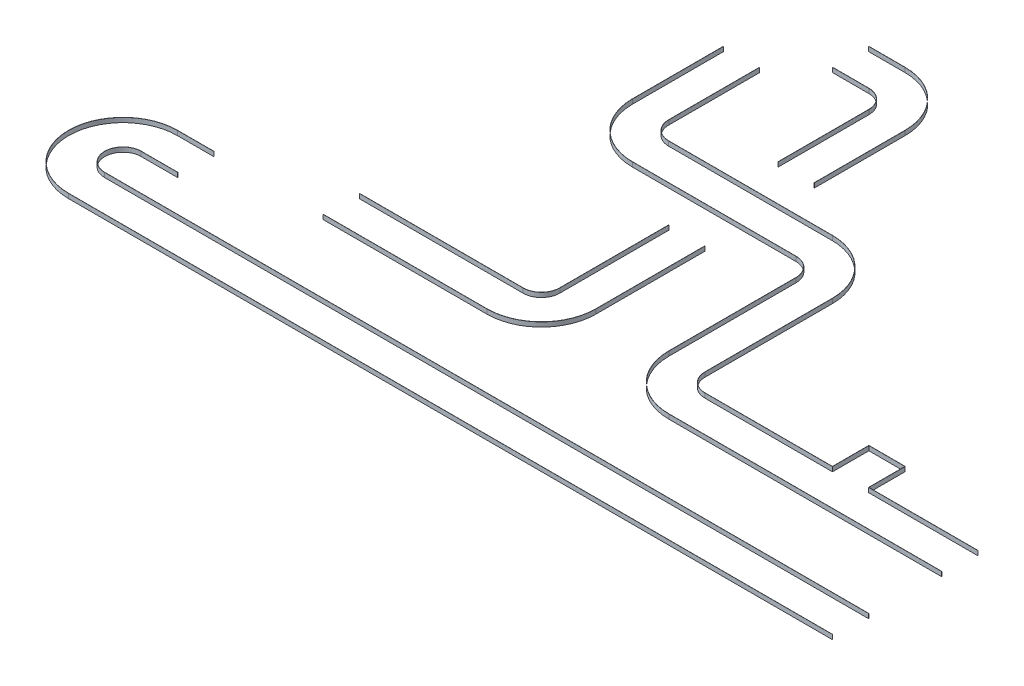
SolidWorks part; units mm, degrees
ref_plane "Front Plane" through (0, 0, 0) normal (0, 0, 1) x (1, 0, 0)
ref_plane "Top Plane" through (0, 0, 0) normal (0, 1, 0) x (1, 0, 0)
ref_plane "Right Plane" through (0, 0, 0) normal (1, 0, 0) x (0, 0, -1)
sketch "Sketch1" plane through (0, 0, 0) normal (0, 1, 0) x (1, 0, 0)
  line L0 (0, 0) -> (-12801.6, 0)
  line L1 (0, 0) -> (0, 609.6)
  line L2 (0, 609.6) -> (-12801.6, 609.6)
  line L3 (-12801.6, 1828.8) -> (-12192, 1828.8)
  line L4 (0, 1828.8) -> (0, 2438.4)
  line L5 (-12192, 1828.8) -> (-12192, 2438.4)
  line L6 (-12192, 2438.4) -> (-7620, 2438.4)
  line L7 (-12801.6, 1219.2) -> (-12192, 1219.2)
  line L8 (-12192, 1219.2) -> (-10363.2, 1219.2)
  line L9 (0, 1828.8) -> (-4572, 1828.8)
  line L10 (-10363.2, 1828.8) -> (-10363.2, 1219.2)
  line L11 (-10363.2, 1828.8) -> (-7620, 1828.8)
  line L12 (0, 2438.4) -> (-1828.8, 2438.4)
  line L13 (-5486.4, 2743.2) -> (-5486.4, 4876.8)
  line L14 (-4876.8, 2743.2) -> (-4876.8, 4876.8)
  line L15 (-5791.2, 5791.2) -> (-8534.4, 5791.2)
  line L16 (-5791.2, 5181.6) -> (-8534.4, 5181.6)
  line L17 (-8839.2, 6096) -> (-8839.2, 7620)
  line L18 (-9448.8, 6096) -> (-9448.8, 7620)
  line L19 (-9448.8, 7620) -> (-9448.8, 8839.2)
  line L20 (-9448.8, 8839.2) -> (-8229.6, 8839.2)
  line L21 (-8839.2, 7620) -> (-8229.6, 7620)
  line L22 (-8229.6, 7620) -> (-8229.6, 8229.6)
  line L23 (-8229.6, 8839.2) -> (-7620, 8839.2)
  line L24 (-8229.6, 8229.6) -> (-7620, 8229.6)
  line L25 (-7315.2, 7924.8) -> (-7315.2, 6400.8)
  line L26 (-6705.6, 7924.8) -> (-6705.6, 6400.8)
  line L27 (-7315.2, 6400.8) -> (-6705.6, 6400.8)
  line L28 (-7315.2, 4572) -> (-7315.2, 2743.2)
  line L29 (-7315.2, 4572) -> (-6705.6, 4572)
  line L30 (-6705.6, 4572) -> (-6705.6, 2743.2)
  line L31 (-2438.4, 2438.4) -> (-4572, 2438.4)
  line L33 (-2438.4, 2438.4) -> (-2438.4, 3048)
  line L34 (-2438.4, 3048) -> (-1828.8, 3048)
  line L35 (-1828.8, 2438.4) -> (-1828.8, 3048)
  arc A0 (-12801.6, 0) -> (-12801.6, 1828.8) centre (-12801.6, 914.4) cw
  arc A1 (-12801.6, 609.6) -> (-12801.6, 1219.2) centre (-12801.6, 914.4) cw
  arc A2 (-4572, 1828.8) -> (-5486.4, 2743.2) centre (-4572, 2743.2) cw
  arc A3 (-4572, 2438.4) -> (-4876.8, 2743.2) centre (-4572, 2743.2) cw
  arc A4 (-4876.8, 4876.8) -> (-5791.2, 5791.2) centre (-5791.2, 4876.8) ccw
  arc A5 (-5486.4, 4876.8) -> (-5791.2, 5181.6) centre (-5791.2, 4876.8) ccw
  arc A6 (-8534.4, 5181.6) -> (-9448.8, 6096) centre (-8534.4, 6096) cw
  arc A7 (-8534.4, 5791.2) -> (-8839.2, 6096) centre (-8534.4, 6096) cw
  arc A8 (-7620, 8839.2) -> (-6705.6, 7924.8) centre (-7620, 7924.8) cw
  arc A9 (-7620, 8229.6) -> (-7315.2, 7924.8) centre (-7620, 7924.8) cw
  arc A10 (-7620, 2438.4) -> (-7315.2, 2743.2) centre (-7620, 2743.2) ccw
  arc A11 (-7620, 1828.8) -> (-6705.6, 2743.2) centre (-7620, 2743.2) ccw
  dimension "D8" = 914.4
  dimension "D9" = 609.6
  dimension "D10" = 304.8
  dimension "D16" = 914.4
  dimension "D17" = 304.8
  dimension "D20" = 914.4
  dimension "D21" = 304.8
  dimension "D25" = 914.4
  dimension "D26" = 304.8
  dimension "D35" = 914.4
  dimension "D36" = 304.8
  dimension "D42" = 914.4
  dimension "D1" = 609.6
  dimension "D2" = 12801.6
  dimension "D3" = 12801.6
  dimension "D4" = 609.6
  dimension "D5" = 12801.6
  dimension "D6" = 609.6
  dimension "D7" = 1219.2
  dimension "D11" = 609.6
  dimension "D12" = 12192
  dimension "D13" = 1828.8
  dimension "D14" = 4572
  dimension "D15" = 3048
  dimension "D18" = 2133.6
  dimension "D19" = 2133.6
  dimension "D22" = 2743.2
  dimension "D23" = 609.6
  dimension "D24" = 609.6
  dimension "D27" = 1524
  dimension "D28" = 1524
  dimension "D29" = 1219.2
  dimension "D30" = 1219.2
  dimension "D31" = 609.6
  dimension "D32" = 609.6
  dimension "D33" = 609.6
  dimension "D34" = 609.6
  dimension "D37" = 609.6
  dimension "D38" = 1524
  dimension "D39" = 609.6
  dimension "D40" = 1828.8
  dimension "D41" = 1828.8
  dimension "D43" = 609.6
  dimension "D44" = 609.6
  dimension "D45" = 609.6
  dimension "D46" = 1828.8
extrude "Boss-Extrude1" add sketch "Sketch1" along normal blind 76.2
sketch "Sketch3" plane through (0, 76.2, 0) normal (0, 1, 0) x (1, 0, 0)
  line L1 (-12192, 2438.4) -> (-10363.2, 2438.4)
  line L2 (-12192, 2438.4) -> (-12192, 1219.2)
  line L3 (-12192, 1219.2) -> (-10363.2, 1219.2)
  line L4 (-10363.2, 2438.4) -> (-10363.2, 1219.2)
  line L5 (-9448.8, 8839.2) -> (-8229.6, 8839.2)
  line L6 (-9448.8, 8839.2) -> (-9448.8, 7620)
  line L7 (-9448.8, 7620) -> (-8229.6, 7620)
  line L8 (-8229.6, 8839.2) -> (-8229.6, 7620)
extrude "Cut-Extrude1" cut sketch "Sketch3" against normal blind 76.2
shell "Shell1" thickness 2.54 removed face at (-9601.2, 0, -914.4) removed face at (-9601.2, 76.2, -914.4)
shell "Shell2" thickness 2.54 removed face at (-7969.4369, 0, -2864.0369) removed face at (-7969.4369, 76.2, -2864.0369)
shell "Shell3" thickness 2.54 removed face at (-5194.2252, 0, -4193.6148) removed face at (-5194.2252, 76.2, -4193.6148)
shell "Shell4" thickness 2.54 removed face at (-7436.0369, 0, -7880.1631) removed face at (-7436.0369, 76.2, -7880.1631)
sketch "Sketch4" plane through (0, 76.2, 0) normal (0, 1, 0) x (1, 0, 0)
  line L0 (0, 0) -> (0, 609.6) construction
  line L1 (-2.54, 607.06) -> (0, 607.06)
  line L2 (-2.54, 607.06) -> (-2.54, 2.54)
  line L3 (-2.54, 2.54) -> (0, 2.54)
  line L4 (0, 607.06) -> (0, 2.54)
  line L5 (0, 1828.8) -> (0, 2438.4) construction
  line L6 (-2.54, 2435.86) -> (0, 2435.86)
  line L7 (-2.54, 2435.86) -> (-2.54, 1831.34)
  line L8 (-2.54, 1831.34) -> (0, 1831.34)
  line L9 (0, 2435.86) -> (0, 1831.34)
  line L11 (-12192, 1828.8) -> (-12192, 1219.2) construction
  line L12 (-12194.54, 1826.26) -> (-12192, 1826.26)
  line L13 (-12194.54, 1826.26) -> (-12194.54, 1221.74)
  line L14 (-12194.54, 1221.74) -> (-12192, 1221.74)
  line L15 (-12192, 1826.26) -> (-12192, 1221.74)
  line L16 (-10363.2, 1828.8) -> (-10363.2, 2438.4) construction
  line L17 (-10360.66, 2435.86) -> (-10363.2, 2435.86)
  line L18 (-10360.66, 2435.86) -> (-10360.66, 1831.34)
  line L19 (-10360.66, 1831.34) -> (-10363.2, 1831.34)
  line L20 (-10363.2, 2435.86) -> (-10363.2, 1831.34)
  line L21 (-6705.6, 4572) -> (-7315.2, 4572) construction
  line L22 (-7312.66, 4569.46) -> (-6708.14, 4569.46)
  line L23 (-7312.66, 4569.46) -> (-7312.66, 4572)
  line L24 (-7312.66, 4572) -> (-6708.14, 4572)
  line L25 (-6708.14, 4569.46) -> (-6708.14, 4572)
  line L26 (-9448.8, 7620) -> (-8839.2, 7620) construction
  line L27 (-9446.26, 7617.46) -> (-8841.74, 7617.46)
  line L28 (-9446.26, 7617.46) -> (-9446.26, 7620)
  line L29 (-9446.26, 7620) -> (-8841.74, 7620)
  line L30 (-8841.74, 7617.46) -> (-8841.74, 7620)
  line L31 (-7315.2, 6400.8) -> (-6705.6, 6400.8) construction
  line L32 (-7312.66, 6403.34) -> (-6708.14, 6403.34)
  line L33 (-7312.66, 6403.34) -> (-7312.66, 6400.8)
  line L34 (-7312.66, 6400.8) -> (-6708.14, 6400.8)
  line L35 (-6708.14, 6403.34) -> (-6708.14, 6400.8)
  line L36 (-8229.6, 8229.6) -> (-8229.6, 8839.2) construction
  line L37 (-8227.06, 8836.66) -> (-8229.6, 8836.66)
  line L38 (-8227.06, 8836.66) -> (-8227.06, 8232.14)
  line L39 (-8227.06, 8232.14) -> (-8229.6, 8232.14)
  line L40 (-8229.6, 8836.66) -> (-8229.6, 8232.14)
extrude "Cut-Extrude3" cut sketch "Sketch4" against normal blind 76.2
